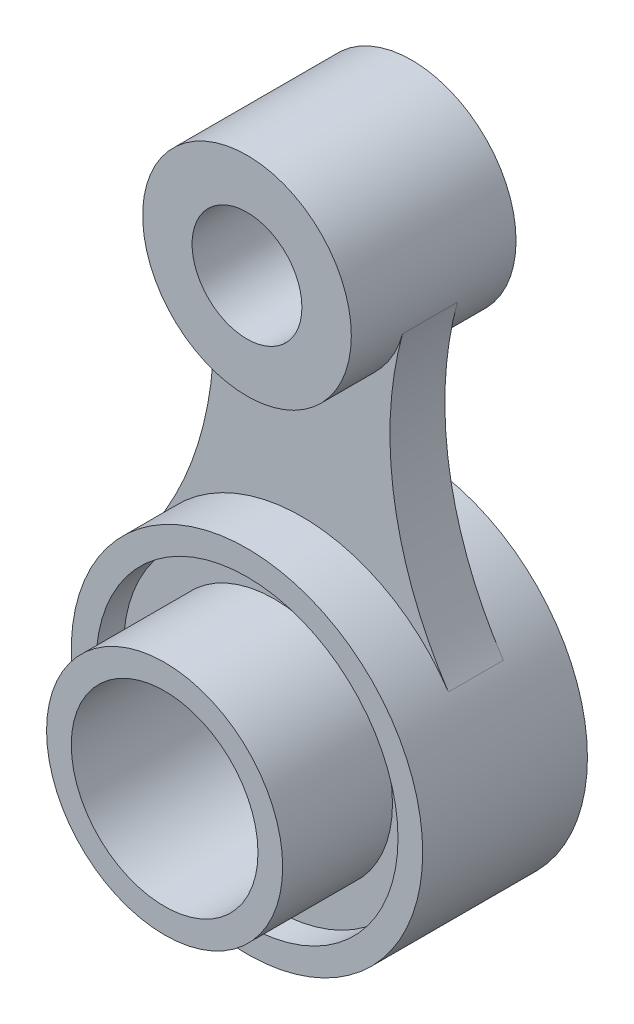
SolidWorks part; units mm, degrees
material "Alliage 1060"
ref_plane "Plan de face" through (0, 0, 0) normal (0, 0, 1) x (1, 0, 0)
ref_plane "Plan de dessus" through (0, 0, 0) normal (0, 1, 0) x (1, 0, 0)
ref_plane "Plan de droite" through (0, 0, 0) normal (1, 0, 0) x (0, 0, -1)
sketch "Esquisse1" plane through (0, 0, 0) normal (0, 0, 1) x (1, 0, 0)
  line L0 (-52.9425, 0) -> (51.7931, 0) construction
  line L1 (0, 103.6789) -> (0, -45.7531) construction
  circle A0 centre (0, 0) radius 17
  circle A1 centre (0, 0) radius 21.5
  circle A2 centre (0, 0) radius 27.5
  circle A3 centre (0, 0) radius 32
  circle A4 centre (0, 75) radius 10
  circle A5 centre (0, 75) radius 19
  arc A6 (18.3212, 69.9669) -> (26.6783, 17.6711) centre (80.0349, 53.0133) ccw
  arc A7 (-18.3212, 69.9669) -> (-26.6783, 17.6711) centre (-80.0349, 53.0133) cw
  dimension "D1" = 64
  dimension "D2" = 55
  dimension "D3" = 43
  dimension "D4" = 34
  dimension "D5" = 38
  dimension "D6" = 20
  dimension "D8" = 64
  dimension "D7" = 75
extrude "Boss.-Extru.1" add sketch "Esquisse1" along normal mid plane 10 contours A5 A7 A3 A6 region at (0, 43.3977, 0)
extrude "Boss.-Extru.2" add sketch "Esquisse1<3>" along normal mid plane 30 contours A5 A4 region at (0, 56.5374, 0)
sketch "Esquisse1<3>" plane through (0, 0, 0) normal (0, 0, 1) x (1, 0, 0) same geometry as "Esquisse1"
extrude "Boss.-Extru.3" add sketch "Esquisse1<5>" along normal blind 30 and the other way blind 15 from offset 0 contours A1 A0 region at (-20.8919, 0, 0)
sketch "Esquisse1<5>" plane through (0, 0, 0) normal (0, 0, 1) x (1, 0, 0) same geometry as "Esquisse1"
extrude "Boss.-Extru.4" add sketch "Esquisse1<6>" along normal mid plane 30 contours A3 A2 | A2 A1 region at (-26.7222, 0, 0) region at (-8.9665, -29.7741, 0)
sketch "Esquisse1<6>" plane through (0, 0, 0) normal (0, 0, 1) x (1, 0, 0) same geometry as "Esquisse1"
extrude "Enlèv. mat.-Extru.1" cut sketch "Esquisse1<7>" along normal blind 5 from offset 10 contours A2 A1 region at (-26.7222, 0, 0)
sketch "Esquisse1<7>" plane through (0, 0, 0) normal (0, 0, 1) x (1, 0, 0) same geometry as "Esquisse1"
